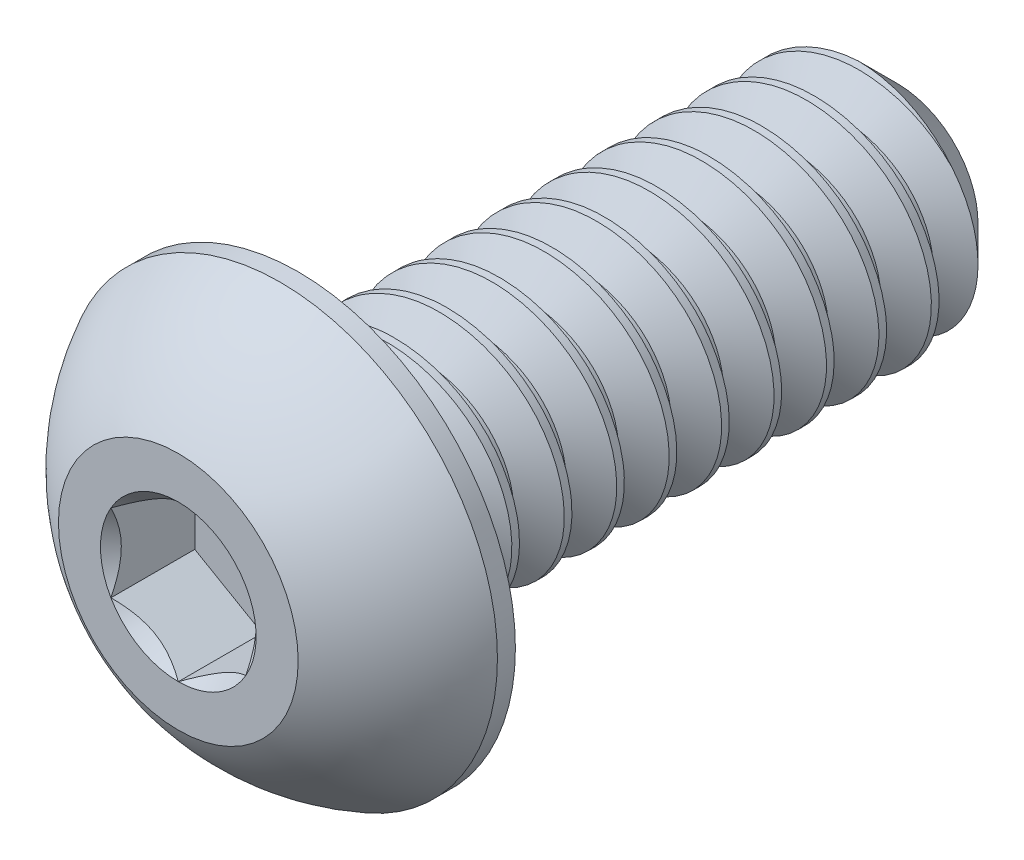
SolidWorks part; units mm, degrees
ref_plane "Front" through (0, 0, 0) normal (0, 0, 1) x (1, 0, 0)
ref_plane "Top" through (0, 0, 0) normal (0, 1, 0) x (1, 0, 0)
ref_plane "Right" through (0, 0, 0) normal (1, 0, 0) x (0, 0, -1)
sketch "Sketch1" plane through (0, 0, 0) normal (1, 0, 0) x (0, 0, -1)
  line L2 (0.8, 0.8) -> (4.8, 0.8)
  line L3 (4.8, 0.8) -> (4.8, 0)
  line L4 (4.8, 0) -> (0.8, 0)
  line L6 (0.68, 1.45) -> (0.8, 1.45) construction
  line L7 (4.8, 0.8) -> (4.8, -0.8) construction
  line L8 (0, 0) -> (0.8, 0) construction
  line L9 (0.8, 1.45) -> (0.8, -1.45) construction
  line L11 (0.8, 0.8) -> (0.8, 0)
  line L13 (0, 0.45) -> (0, -0.45) construction
  line L14 (0, 0.45) -> (0, 0.8) construction
  arc A3 (0, 0.8) -> (0.68, 1.45) centre (1.4154, 0) cw construction
  dimension "D1" = 0.12
revolve "Revolve1" add sketch "Sketch1" angle 360 mid plane about L4
sketch "Sketch3" plane through (0, 0, -4.8) normal (0, 0, -1) x (-1, 0, 0)
  circle A0 centre (0, 0) radius 0.8
curve "Helix/Spiral1" pitch 0.35 height 4.35 radius 0.8 centre (0, 0, -4.8) axis (0, 0, 1) start towards (0, 1, 0)
chamfer "Chamfer1" distance 0.2625 angle 45 1 edges at (0, 0.8, -4.8)
sketch "Sketch7" plane through (0, 0, 0) normal (1, 0, 0) x (0, 0, -1)
  line L6 (0.68, 1.45) -> (0.8, 1.45) construction
  line L8 (0, 0) -> (0.8, 0) construction
  line L11 (0.8, 1.45) -> (0.8, -1.45) construction
  line L12 (0.68, 1.45) -> (0.8, 1.45)
  line L13 (0, 0) -> (0.8, 0)
  line L14 (0, 0.45) -> (0, -0.45) construction
  line L15 (0.8, 1.45) -> (0.8, 0)
  line L16 (0, 0.8) -> (0, 0)
  arc A2 (0.68, 1.45) -> (0, 0.8) centre (1.4154, 0) ccw construction
  arc A3 (0.68, 1.45) -> (0, 0.8) centre (1.4154, 0) ccw
revolve "Revolve2" add sketch "Sketch7" angle 360 mid plane about L13
sketch "Sketch5" plane through (0, 0, 0) normal (0, 0, 1) x (1, 0, 0)
  line L1 (0.45, -0.2598) -> (0.45, 0.2598)
  line L2 (0.45, 0.2598) -> (0, 0.5196)
  line L3 (0, 0.5196) -> (-0.45, 0.2598)
  line L4 (-0.45, 0.2598) -> (-0.45, -0.2598)
  line L5 (-0.45, -0.2598) -> (0, -0.5196)
  line L6 (0, -0.5196) -> (0.45, -0.2598)
  circle A0 centre (0, 0) radius 0.45 construction
extrude "Cut-Extrude2" cut sketch "Sketch5" against normal blind 0.56
sketch "Sketch6" plane through (0, 0, 0) normal (0, 0, 1) x (1, 0, 0)
  circle A0 centre (0, 0) radius 0.5196
extrude "Cut-Extrude3" cut sketch "Sketch6" against normal blind 0.56 draft 45
sketch "Sketch2" plane through (0, 0, 0) normal (1, 0, 0) x (0, 0, -1)
  line L0 (4.5375, 0.8) -> (4.8368, 0.8)
  line L1 (4.8368, 0.8) -> (4.7125, 0.5848)
  line L2 (4.7125, 0.5848) -> (4.6618, 0.5848)
  line L3 (4.6618, 0.5848) -> (4.5375, 0.8)
  line L4 (4.5996, 0.6924) -> (4.7746, 0.6924) construction
  dimension "D1" = 60
  dimension "D2" = 0.0508
  dimension "D3" = 0.175
sweep "Cut-Sweep1" cut profiles "Sketch2" path "Helix/Spiral1"
ref_axis "Center Axis 1" through (0, 0, -5.0796) along (0, 0, 1)
ref_plane "Contact Plane 1" through (0, 0, -0.8) normal (0, 0, -1) x (-1, 0, 0)
ref_plane "Contact Plane 2" through (0, 0, 0) normal (0, 0, 1) x (1, 0, 0)
equation "\"D3@Helix/Spiral1\" = \"Lg@Sketch1\" + \"D4@Helix/Spiral1\""
equation "\"D2@Sketch2\"=\"D4@Helix/Spiral1\" * .145"
equation "\"D3@Sketch2\" = \"D4@Helix/Spiral1\" * .5"
equation "\"D1@Chamfer1\" = \"D4@Helix/Spiral1\" * .75"
equation "\"D1@Cut-Extrude2\" = \"Head Ht@Sketch1\" * .7"
equation "\"D1@Sketch1\" = \"Head Ht@Sketch1\" * .15"
equation "\"D1@Cut-Extrude3\" = \"D1@Cut-Extrude2\""
